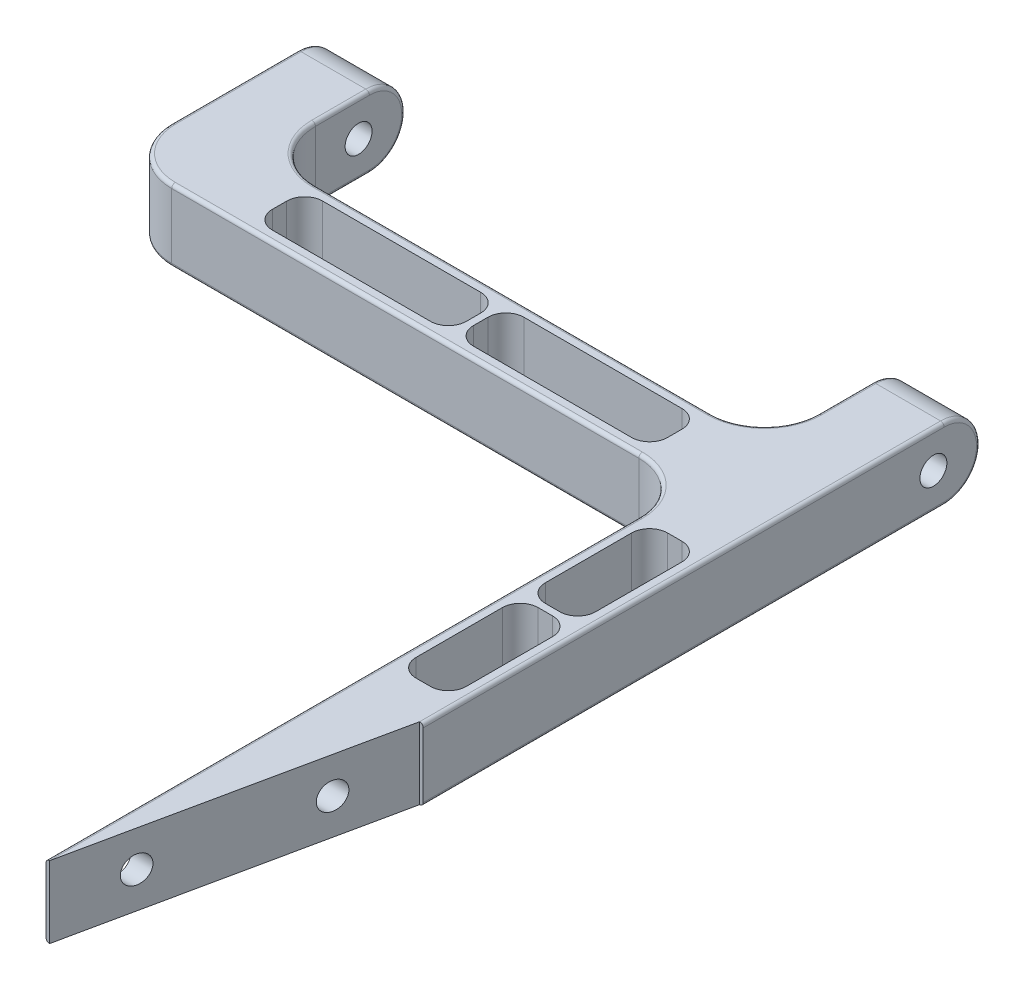
SolidWorks part; units mm, degrees
material "6061-T6 (SS)"
ref_plane "Front Plane" through (0, 0, 0) normal (0, 0, 1) x (1, 0, 0)
ref_plane "Top Plane" through (0, 0, 0) normal (0, 1, 0) x (1, 0, 0)
ref_plane "Right Plane" through (0, 0, 0) normal (1, 0, 0) x (0, 0, -1)
sketch "Sketch1" plane through (0, 0, 0) normal (0, 1, 0) x (1, 0, 0)
  line L0 (44.45, -6.35) -> (184.15, -6.35)
  line L3 (0, 44.45) -> (25.4, 44.45)
  line L4 (25.4, 12.7) -> (25.4, 44.45)
  line L6 (184.15, -31.75) -> (19.05, -31.75)
  line L8 (0, 44.45) -> (0, -12.7)
  line L9 (203.2, 44.45) -> (228.6, 44.45)
  line L10 (203.2, 44.45) -> (203.2, 12.7)
  line L11 (203.2, -260.35) -> (228.6, -260.35)
  line L12 (228.6, 44.45) -> (228.6, -260.35)
  line L13 (203.2, -50.8) -> (203.2, -260.35)
  arc A0 (203.2, 12.7) -> (184.15, -6.35) centre (184.15, 12.7) cw
  arc A1 (19.05, -31.75) -> (0, -12.7) centre (19.05, -12.7) cw
  arc A2 (44.45, -6.35) -> (25.4, 12.7) centre (44.45, 12.7) cw
  arc A3 (203.2, -50.8) -> (184.15, -31.75) centre (184.15, -50.8) ccw
  point P5 (203.2, -31.75)
  dimension "D6" = 19.05
  dimension "D4" = 19.05
  dimension "D1" = 25.4
  dimension "D2" = 25.4
  dimension "D3" = 25.4
  dimension "D5" = 50.8
  dimension "D7" = 304.8
  dimension "D8" = 228.6
  dimension "D9" = 50.8
extrude "Boss-Extrude1" add sketch "Sketch1" along normal blind 25.4
sketch "Sketch2" plane through (0, 0, 260.35) normal (0, 0, 1) x (1, 0, 0)
  line L6 (203.2, 0) -> (228.6, 0) construction
  line L12 (228.6, 25.4) -> (215.9, 25.4)
  line L17 (228.6, 25.4) -> (228.6, 0)
  line L18 (228.6, 0) -> (215.9, 0)
  line L19 (215.9, 25.4) -> (215.9, 0)
sketch "Sketch3" plane through (0, 25.4, 0) normal (0, 1, 0) x (1, 0, 0)
  line L0 (228.6, -260.35) -> (215.9, -260.35) construction
  line L1 (228.6, -260.35) -> (215.9, -260.35)
  line L2 (227.33, -152.4) -> (204.47, -260.35)
  line L3 (227.33, -152.4) -> (228.6, -152.4)
  line L4 (228.6, -260.35) -> (228.6, 44.45) construction
  line L10 (203.2, -50.8) -> (203.2, -260.35)
  line L11 (203.2, -260.35) -> (228.6, -260.35)
  line L12 (228.6, -260.35) -> (228.6, 44.45)
  line L13 (228.6, 44.45) -> (203.2, 44.45)
  line L14 (203.2, 44.45) -> (203.2, 12.7)
  line L15 (184.15, -6.35) -> (44.45, -6.35)
  line L16 (25.4, 12.7) -> (25.4, 44.45)
  line L17 (25.4, 44.45) -> (0, 44.45)
  line L18 (0, 44.45) -> (0, -12.7)
  line L19 (19.05, -31.75) -> (184.15, -31.75)
  line L20 (203.2, -50.8) -> (203.2, -260.35)
  line L21 (203.2, -260.35) -> (228.6, -260.35)
  line L22 (228.6, -260.35) -> (228.6, 44.45)
  line L23 (228.6, 44.45) -> (203.2, 44.45)
  line L24 (203.2, 44.45) -> (203.2, 12.7)
  line L25 (184.15, -6.35) -> (44.45, -6.35)
  line L26 (25.4, 12.7) -> (25.4, 44.45)
  line L27 (25.4, 44.45) -> (0, 44.45)
  line L28 (0, 44.45) -> (0, -12.7)
  line L29 (19.05, -31.75) -> (184.15, -31.75)
  arc A4 (203.2, -50.8) -> (184.15, -31.75) centre (184.15, -50.8) ccw
  arc A5 (184.15, -6.35) -> (203.2, 12.7) centre (184.15, 12.7) ccw
  arc A6 (25.4, 12.7) -> (44.45, -6.35) centre (44.45, 12.7) ccw
  arc A7 (0, -12.7) -> (19.05, -31.75) centre (19.05, -12.7) ccw
  arc A8 (203.2, -50.8) -> (184.15, -31.75) centre (184.15, -50.8) ccw
  arc A9 (184.15, -6.35) -> (203.2, 12.7) centre (184.15, 12.7) ccw
  arc A10 (25.4, 12.7) -> (44.45, -6.35) centre (44.45, 12.7) ccw
  arc A11 (0, -12.7) -> (19.05, -31.75) centre (19.05, -12.7) ccw
  dimension "D2" = 107.95
  dimension "D3" = 1.27
  dimension "D4" = 1.27
  dimension "D1" = 0
extrude "Cut-Extrude3" cut sketch "Sketch3" against normal up to next
fillet "Fillet1" radius 1.27 26 edges at (0, 12.7, -44.45) (25.4, 12.7, -44.45) (203.2, 12.7, -44.45) (228.6, 12.7, -44.45) (228.6, 0, 53.975) (203.2, 0, 155.575) (197.6204, 0, 37.3296) (5.5796, 0, 26.1704) (101.6, 0, 31.75) (197.6204, 0, 0.7704) (203.2, 0, -28.575) (114.3, 0, 6.35) (30.9796, 0, 0.7704) (25.4, 0, -28.575) (0, 0, -15.875) (25.4, 25.4, -28.575) (30.9796, 25.4, 0.7704) (114.3, 25.4, 6.35) (197.6204, 25.4, 0.7704) (203.2, 25.4, -28.575) (228.6, 25.4, 53.975) (203.2, 25.4, 155.575) (197.6204, 25.4, 37.3296) (101.6, 25.4, 31.75) (5.5796, 25.4, 26.1704) (0, 25.4, -15.875)
sketch "Sketch4" plane through (203.2, 0, 0) normal (-1, 0, 0) x (0, 0, 1)
  line L0 (50.8, 12.7) -> (260.35, 12.7)
  line L1 (50.8, 24.13) -> (50.8, 1.27) construction
  line L2 (260.35, 25.4) -> (260.35, 0) construction
  line L3 (152.4, 0) -> (152.4, 25.4) construction
  line L4 (152.4, 0) -> (152.4, 25.4)
  circle A0 centre (177.8, 12.7) radius 4.7625
  circle A1 centre (234.95, 12.7) radius 4.7625
  dimension "D3" = 9.525
  dimension "D4" = 9.525
  dimension "D1" = 25.4
  dimension "D2" = 25.4
extrude "Cut-Extrude4" cut sketch "Sketch4" against normal up to next contours L0 A0 | L0 A0 | A1
sketch "Sketch16" plane through (0, 25.4, 0) normal (0, 1, 0) x (1, 0, 0)
  line L0 (64.7613, -351.7333) -> (140.9613, -351.7333)
  line L1 (64.7613, -72.3333) -> (140.9613, -72.3333)
  line L2 (64.7613, -72.3333) -> (64.7613, -631.1333)
  line L3 (64.7613, -631.1333) -> (140.9613, -631.1333)
  line L4 (140.9613, -72.3333) -> (140.9613, -631.1333)
  line L5 (140.9613, -351.7333) -> (235.7641, -351.7333)
  dimension "D1" = 558.8
  dimension "D2" = 76.2
fillet "Fillet2" radius 12.7 12 edges at (0.372, 25.028, -44.078) (25.028, 25.028, -44.078) (203.572, 0.372, -44.078) (228.228, 0.372, -44.078) (203.572, 25.028, -44.078) (228.228, 25.028, -44.078) (215.9, 25.4, -44.45) (215.9, 0, -44.45) (12.7, 25.4, -44.45) (0.372, 0.372, -44.078) (25.028, 0.372, -44.078) (12.7, 0, -44.45)
sketch "Sketch17" plane through (203.2, 0, 0) normal (-1, 0, 0) x (0, 0, 1)
  line L0 (-12.7, 24.13) -> (-31.75, 24.13) construction
  line L1 (-43.18, 15.875) -> (-43.18, 9.525) construction
  circle A0 centre (-27.94, 12.7) radius 4.7625
  dimension "D1" = 9.525
  dimension "D2" = 11.43
  dimension "D3" = 15.24
extrude "Cut-Extrude5" cut sketch "Sketch17" against normal through all and the other way through all contours A0
sketch "Sketch18" plane through (0, 25.4, 0) normal (0, 1, 0) x (1, 0, 0)
  line L0 (44.45, -7.62) -> (184.15, -7.62)
  line L1 (184.15, -7.62) -> (227.33, -7.62)
  line L2 (227.33, -152.4) -> (227.33, 31.75) construction
  line L4 (184.15, -30.48) -> (184.15, -7.62)
  line L5 (44.45, -30.48) -> (44.45, -7.62)
  line L6 (44.45, -30.48) -> (184.15, -30.48)
  line L7 (204.47, -50.8) -> (227.33, -50.8)
  line L8 (227.33, -50.8) -> (227.33, -139.7)
  line L9 (227.33, -139.7) -> (204.47, -139.7)
  line L10 (204.47, -50.8) -> (204.47, -260.35) construction
  line L11 (204.47, -139.7) -> (204.47, -50.8)
  line L16 (44.45, -27.94) -> (184.15, -27.94)
  line L17 (114.3, -10.16) -> (114.3, -27.94)
  line L18 (184.15, -10.16) -> (44.45, -10.16)
  line L19 (113.03, -10.16) -> (113.03, -27.94)
  line L20 (115.57, -10.16) -> (115.57, -27.94)
  line L21 (204.47, -95.25) -> (227.33, -95.25)
  line L22 (204.47, -96.52) -> (227.33, -96.52)
  line L23 (204.47, -93.98) -> (227.33, -93.98)
  line L24 (207.01, -50.8) -> (207.01, -139.7)
  line L25 (224.79, -50.8) -> (224.79, -139.7)
  line M19 (227.33, -152.4) -> (227.33, 31.75)
  line M31 (204.47, -50.8) -> (204.47, -260.35)
  dimension "D1" = 12.7
  dimension "D2" = 2.54
  dimension "D3" = 2.54
  dimension "D4" = 1.27
  dimension "D5" = 1.27
  dimension "D8" = 2.54
  dimension "D9" = 2.54
  dimension "D6" = 1.27
  dimension "D7" = 1.27
extrude "Cut-Extrude6" cut sketch "Sketch18" against normal blind 19.05 contours L22 L9 M31 M19 | L23 L7 M31 M19 | L18 L20 L16 L4 | L19 L18 L5 L16
fillet "Fillet3" radius 6.35 16 edges at (207.01, 15.875, 93.98) (224.79, 15.875, 93.98) (224.79, 15.875, 139.7) (207.01, 15.875, 139.7) (207.01, 15.875, 96.52) (224.79, 15.875, 96.52) (224.79, 15.875, 50.8) (207.01, 15.875, 50.8) (184.15, 15.875, 27.94) (184.15, 15.875, 10.16) (115.57, 15.875, 27.94) (115.57, 15.875, 10.16) (113.03, 15.875, 27.94) (113.03, 15.875, 10.16) (44.45, 15.875, 27.94) (44.45, 15.875, 10.16)
